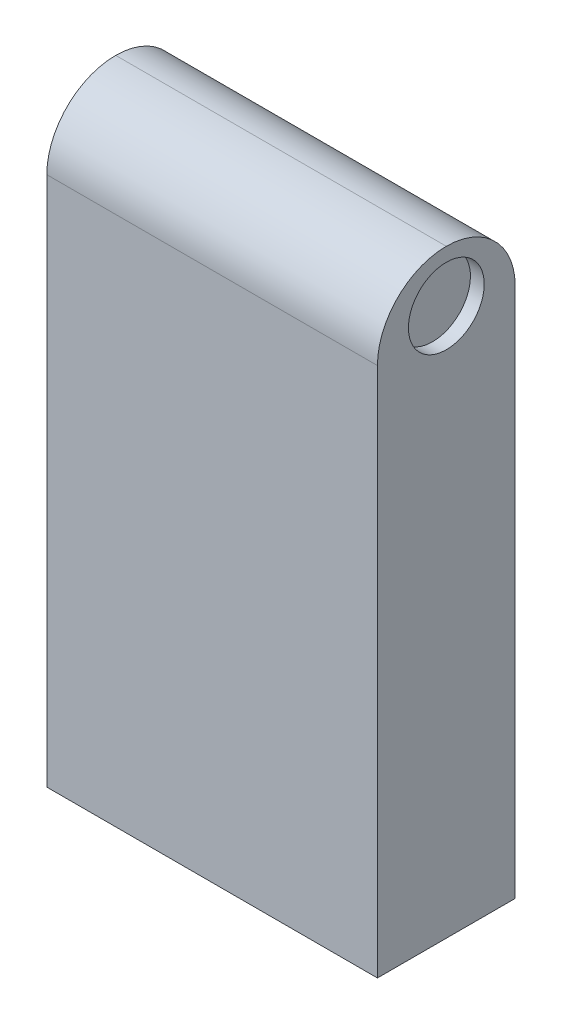
SolidWorks part; units mm, degrees
ref_plane "Front Plane" through (0, 0, 0) normal (0, 0, 1) x (1, 0, 0)
ref_plane "Top Plane" through (0, 0, 0) normal (0, 1, 0) x (1, 0, 0)
ref_plane "Right Plane" through (0, 0, 0) normal (1, 0, 0) x (0, 0, -1)
sketch "Sketch1" plane through (0, 0, 0) normal (0, 0, 1) x (1, 0, 0)
  line L1 (0, 0) -> (24, 0)
  line L2 (0, 0) -> (0, 43.5)
  line L3 (0, 43.5) -> (24, 43.5)
  line L4 (24, 0) -> (24, 43.5)
  dimension "D1" = 43.5
  dimension "D2" = 24
extrude "Boss-Extrude1" add sketch "Sketch1" along normal blind 10
fillet "Fillet1" radius 5 2 edges at (12, 43.5, 0) (12, 43.5, 10)
sketch "Sketch2" plane through (24, 0, 0) normal (1, 0, 0) x (0, 0, -1)
  line L0 (-5, 43.5) -> (-5, 12.9041) construction
  circle A0 centre (-5, 39.7454) radius 2.75
  dimension "D1" = 5.5
extrude "Cut-Extrude1" cut sketch "Sketch2" against normal blind 1
